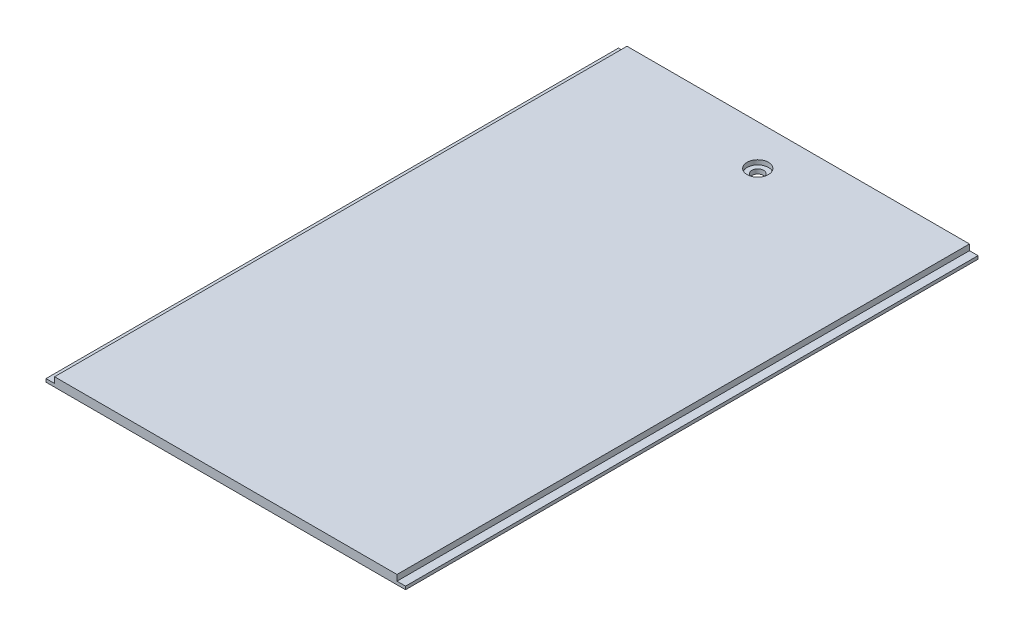
SolidWorks part; units mm, degrees
material "PLA"
ref_plane "Спереди" through (0, 0, 0) normal (0, 0, 1) x (1, 0, 0)
ref_plane "Сверху" through (0, 0, 0) normal (0, 1, 0) x (1, 0, 0)
ref_plane "Справа" through (0, 0, 0) normal (1, 0, 0) x (0, 0, -1)
sketch "Эскиз1" plane through (0, 0, 0) normal (0, 1, 0) x (1, 0, 0)
  line L1 (38.075, 63.65) -> (-38.075, 63.65)
  line L2 (38.075, 63.65) -> (38.075, -63.65)
  line L3 (38.075, -63.65) -> (-38.075, -63.65)
  line L4 (-38.075, 63.65) -> (-38.075, -63.65)
  line L5 (38.075, 63.65) -> (-38.075, -63.65) construction
  line L6 (38.075, -63.65) -> (-38.075, 63.65) construction
  point P0 (0, 0)
  dimension "D1" = 76.15
  dimension "D2" = 127.3
extrude "Бобышка-Вытянуть1" add sketch "Эскиз1" along normal blind 2
sketch "Эскиз2" plane through (0, 0, 63.65) normal (0, 0, 1) x (1, 0, 0)
  line L0 (0, 0) -> (0, -50000) construction
  line L1 (-38.075, 0) -> (-39.975, 0)
  line L2 (-38.075, 0) -> (-38.075, 0.7)
  line L3 (-38.075, 0.7) -> (-39.975, 0.7)
  line L4 (-39.975, 0) -> (-39.975, 0.7)
  line L5 (38.075, 0.7) -> (39.975, 0.7)
  line L6 (39.975, 0) -> (39.975, 0.7)
  line L7 (38.075, 0) -> (39.975, 0)
  line L8 (38.075, 0) -> (38.075, 0.7)
  dimension "D1" = 0.7
  dimension "D2" = 1.9
extrude "Бобышка-Вытянуть2" add sketch "Эскиз2" against normal up to surface (127.3 mm away) up to face at (0, 1, -63.65)
sketch "Эскиз3" plane through (0, 2, 0) normal (0, 1, 0) x (1, 0, 0)
  line L0 (0, 0) -> (0, 50000) construction
  line L1 (38.075, 63.65) -> (-38.075, 63.65) construction
  circle A0 centre (0, 54.65) radius 1.3
  dimension "D1" = 2.6
  dimension "D2" = 9
extrude "Вырез-Вытянуть1" cut sketch "Эскиз3" against normal through all
sketch "Эскиз5" plane through (0, 2, 0) normal (0, 1, 0) x (1, 0, 0)
  circle A0 centre (0, 54.65) radius 2.375
  dimension "D1" = 4.75
extrude "Вырез-Вытянуть2" cut sketch "Эскиз5" against normal blind 1
